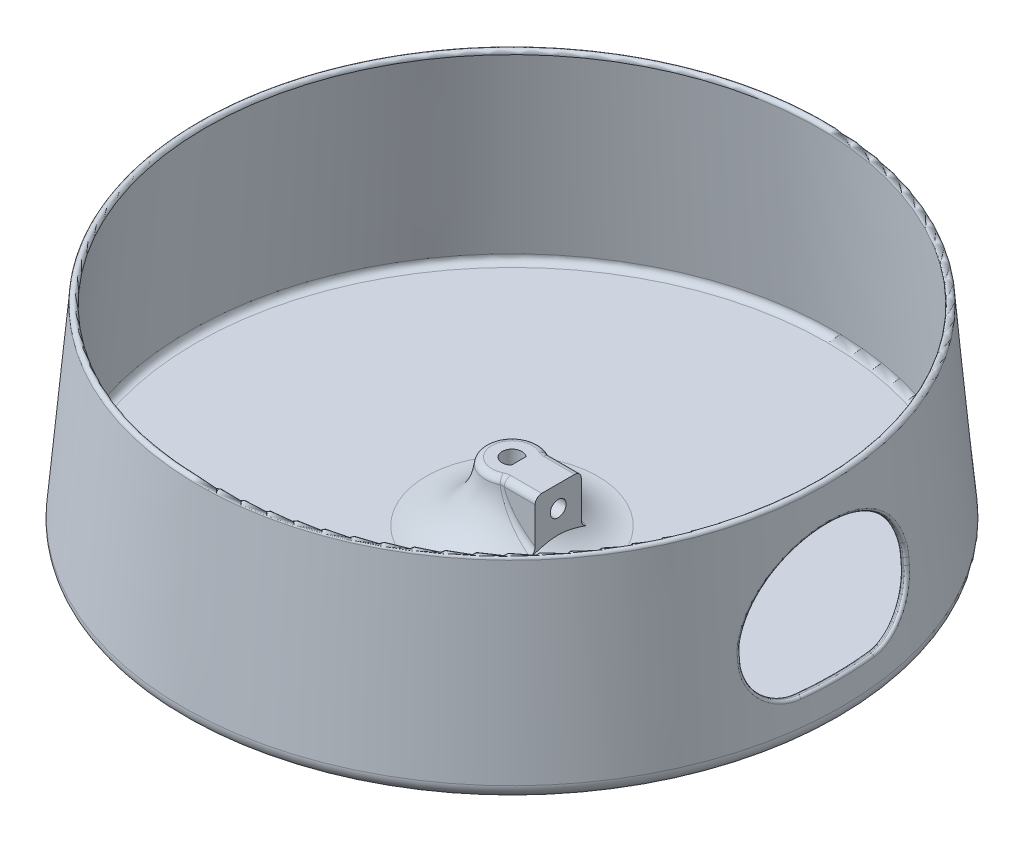
SolidWorks part; units mm, degrees
ref_plane "Front" through (0, 0, 0) normal (0, 0, 1) x (1, 0, 0)
ref_plane "Top" through (0, 0, 0) normal (0, 1, 0) x (1, 0, 0)
ref_plane "Right" through (0, 0, 0) normal (1, 0, 0) x (0, 0, -1)
sketch "Esquisse2" plane through (0, 0, 0) normal (0, 0, 1) x (1, 0, 0)
  line L0 (0, 0) -> (47.944, 0)
  line L1 (49.9363, 2.1743) -> (47.4981, 30.0436)
  line L2 (46.5019, 29.9564) -> (48.9401, 2.0872)
  line L3 (47.944, 1) -> (13, 1)
  line L4 (4, 10) -> (0, 10)
  line L5 (0, 10) -> (0, 0)
  line L6 (0, 10) -> (0, 20) construction
  arc A0 (47.944, 0) -> (49.9363, 2.1743) centre (47.944, 2) ccw
  arc A1 (47.4981, 30.0436) -> (46.5019, 29.9564) centre (47, 30) ccw
  arc A2 (48.9401, 2.0872) -> (47.944, 1) centre (47.944, 2) cw
  arc A3 (13, 1) -> (4, 10) centre (13, 10) cw
  dimension "D1" = 1
  dimension "D3" = 1
  dimension "D4" = 2
  dimension "D8" = 30
  dimension "D9" = 94
  dimension "D10" = 99.8879
  dimension "D2" = 1
  dimension "D5" = 10
  dimension "D6" = 8
  dimension "D7" = 85
revolve "Révolution1" add sketch "Esquisse2" angle 360 about L6
sketch "Esquisse3" plane through (0, 10, 0) normal (0, 1, 0) x (1, 0, 0)
  line L0 (1, 1.118) -> (1, -1.118)
  arc A0 (1, 1.118) -> (1, -1.118) centre (0, 0) ccw
  dimension "D1" = 3
  dimension "D2" = 1
extrude "Enlèv. mat.-Extru.1" cut sketch "Esquisse3" against normal blind 6.5
sketch "Esquisse4" plane through (1, 0, 0) normal (-1, 0, 0) x (0, 0, 1)
  line L0 (1.118, 10) -> (-1.118, 10) construction
  line L1 (3.5, 10) -> (-3.5, 10)
  line L2 (3.5, 10) -> (3.5, 0)
  line L3 (3.5, 0) -> (-3.5, 0)
  line L4 (-3.5, 10) -> (-3.5, 0)
  dimension "D1" = 7
extrude "Boss.-Extru.1" add sketch "Esquisse4" against normal blind 6
sketch "Esquisse5" plane through (7, 0, 0) normal (1, 0, 0) x (0, 0, -1)
  line L0 (-3.5, 10) -> (3.5, 10) construction
  circle A0 centre (0, 6.75) radius 1.2
  dimension "D1" = 3.25
  dimension "D2" = 2.4
extrude "Enlèv. mat.-Extru.2" cut sketch "Esquisse5" against normal blind 7
fillet "Congé1" radius 1 5 edges at (4.4682, 10, 3.5) (-4, 10, 0) (4.4682, 10, -3.5) (3.2799, 6.298, -3.5) (2.1985, 8.4572, 3.5)
sketch "Esquisse6" plane through (0, 0, 0) normal (0, 0, 1) x (1, 0, 0)
  line L1 (49.9363, 21) -> (39.9363, 21)
  line L2 (49.9363, 21) -> (49.9363, 6)
  line L3 (49.9363, 6) -> (39.9363, 6)
  line L4 (39.9363, 21) -> (39.9363, 6)
  dimension "D1" = 10
  dimension "D2" = 6
  dimension "D3" = 15
extrude "Enlèv. mat.-Extru.3" cut sketch "Esquisse6" against normal mid plane 25
fillet "Congé2" radius 7 4 edges at (47.4817, 6, -12.5) (46.1234, 21, -12.5) (46.1234, 21, 12.5) (47.4817, 6, 12.5)
sketch "Esquisse7" plane through (7, 0, 0) normal (1, 0, 0) x (0, 0, -1)
  line L0 (-12.2082, 16) -> (12.2082, 16)
  line L1 (5.5, 6) -> (-5.5, 6) construction
  arc A0 (12.2082, 16) -> (-12.2082, 16) centre (0, 12.3602) ccw
  arc A4 (12.5, 14) -> (5.5, 21) centre (5.5, 14) ccw construction
  arc A5 (-5.5, 21) -> (-12.5, 14) centre (-5.5, 14) ccw construction
  arc A6 (12.5, 14) -> (5.5, 21) centre (5.5, 14) ccw construction
  dimension "D1" = 10
extrude "Enlèv. mat.-Extru.4" cut sketch "Esquisse7" along normal through all
fillet "Congé3" radius 0.4 16 edges at (47.4525, 7.519, -9.8542) (48.5978, 6, 0) (47.0948, 8.6767, 11.0053) (48.4774, 7.5189, 9.8541) (49.6016, 6, 0) (48.126, 8.6735, -11.0029) (46.9227, 25.0771, 0.7545) (47.9266, 25.0769, -0.757)
